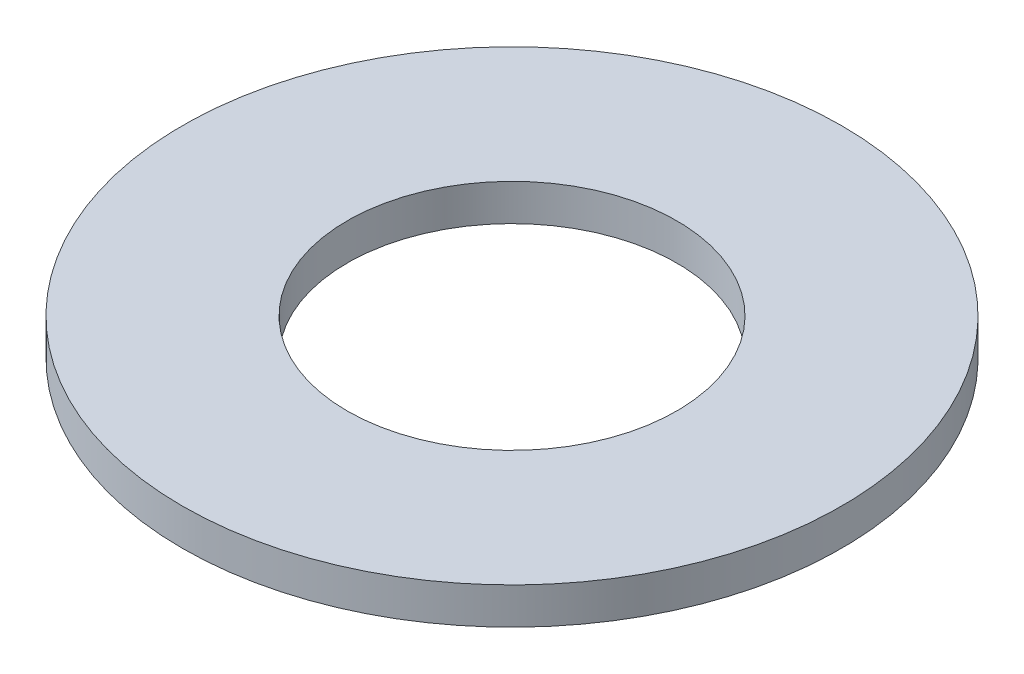
SolidWorks part; units mm, degrees
ref_plane "Front Plane" through (0, 0, 0) normal (0, 0, 1) x (1, 0, 0)
ref_plane "Top Plane" through (0, 0, 0) normal (0, 1, 0) x (1, 0, 0)
ref_plane "Right Plane" through (0, 0, 0) normal (1, 0, 0) x (0, 0, -1)
sketch "Sketch1" plane through (0, 0, 0) normal (0, 1, 0) x (1, 0, 0)
  circle A0 centre (0, 0) radius 45
  dimension "FLANGE_OD" = 90
extrude "Boss-Extrude1" add sketch "Sketch1" along normal blind 5
sketch "Sketch2" plane through (0, 0, 0) normal (0, 1, 0) x (1, 0, 0)
  circle A0 centre (0, 0) radius 22.5
  dimension "BORE_D" = 45
extrude "Cut-Extrude1" cut sketch "Sketch2" along normal through all
sketch "Sketch3" plane through (0, 5, 0) normal (0, 1, 0) x (1, 0, 0)
  circle A0 centre (0, 0) radius 17.3923 construction
  circle A1 centre (-17.3923, 0) radius 2.3276
  dimension "BOLT_D" = 4.6552
  dimension "BOLT_PCD" = 34.7846
extrude "Cut-Extrude2" cut sketch "Sketch3" against normal blind 4.4911 rebuild error yes
pattern_circular "CirPattern1" count 4 over 360 rebuild error yes
